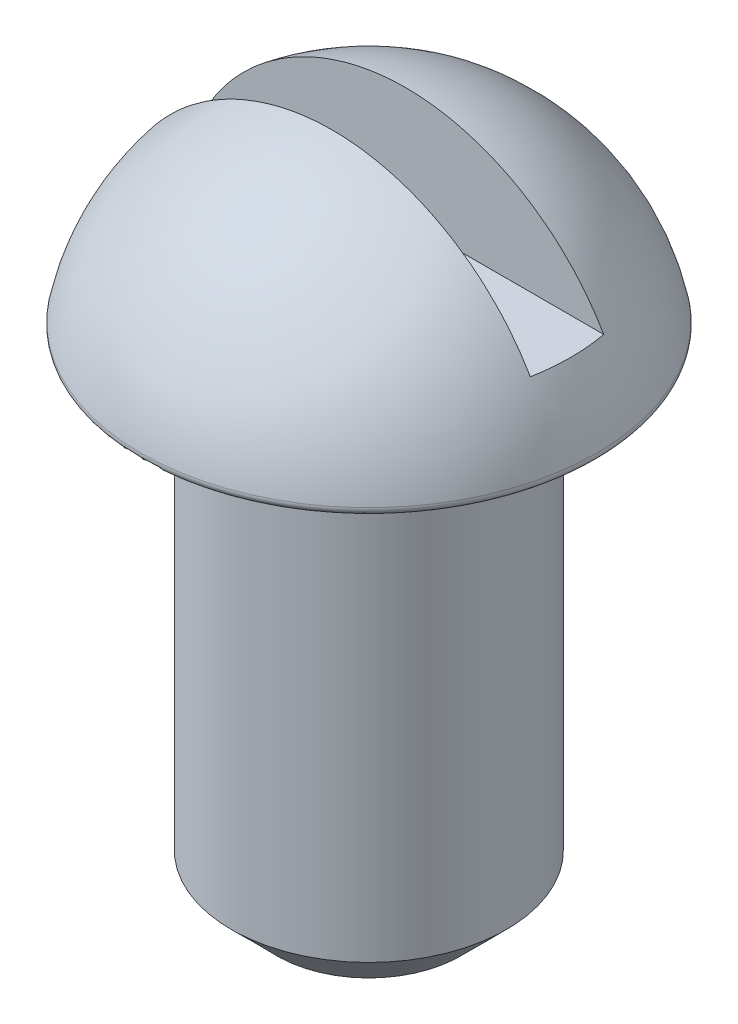
SolidWorks part; units mm, degrees
ref_plane "Спереди" through (0, 0, 0) normal (0, 0, 1) x (1, 0, 0)
ref_plane "Сверху" through (0, 0, 0) normal (0, 1, 0) x (1, 0, 0)
ref_plane "Справа" through (0, 0, 0) normal (1, 0, 0) x (0, 0, -1)
sketch "Эскиз1" plane through (0, 0, 0) normal (0, 0, 1) x (1, 0, 0)
  line L0 (0, 125.7632) -> (0, 0) construction
  line L1 (3, 90.0493) -> (5, 90.0493)
  line L2 (0, 94.2493) -> (0, 79.2493)
  line L3 (0, 94.2493) -> (0.8, 94.2493)
  line L4 (3, 90.0493) -> (3, 79.2493)
  line L6 (3, 79.2493) -> (0, 79.2493)
  arc A0 (0.8, 94.2493) -> (5, 90.0493) centre (-0.0317, 89.2176) cw
  dimension "D1" = 0.8
  dimension "D2" = 4.2
  dimension "D3" = 15
  dimension "D4" = 5.1
  dimension "D5" = 3
  dimension "D6" = 5
revolve "Повернуть1" add sketch "Эскиз1" angle 360 about L0
ref_axis "Ось4" through (0, 0.7467, 0) along (0, -1, 0)
sketch "Эскиз13" plane through (0, 94.2493, 0) normal (0, 1, 0) x (-1, 0, 0)
  line L1 (5, -0.8) -> (-5, -0.8)
  line L2 (5, -0.8) -> (5, 0.8)
  line L3 (5, 0.8) -> (-5, 0.8)
  line L4 (-5, -0.8) -> (-5, 0.8)
  dimension "D1" = 5
  dimension "D2" = 10
  dimension "D3" = 0.8
  dimension "D4" = 1.6
extrude "Вырез-Вытянуть9" cut sketch "Эскиз13" against normal blind 2.5
fillet "Скругление1" radius 0.15 1 edges at (-5, 90.0493, 0)
chamfer "Фаска1" distance 1 angle 45 1 edges at (-3, 79.2493, 0)
